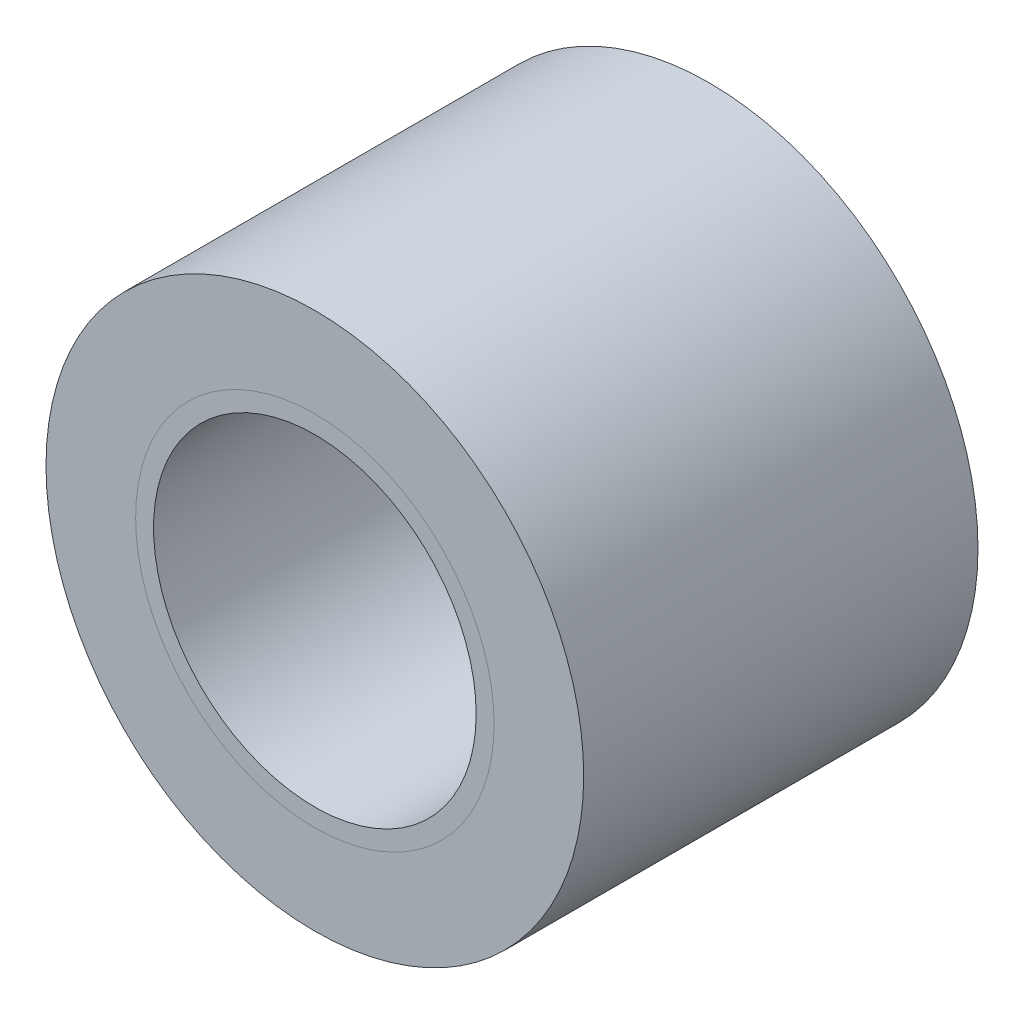
SolidWorks part; units mm, degrees
ref_plane "Plan de face" through (0, 0, 0) normal (0, 0, 1) x (1, 0, 0)
ref_plane "Plan de dessus" through (0, 0, 0) normal (0, 1, 0) x (1, 0, 0)
ref_plane "Plan de droite" through (0, 0, 0) normal (1, 0, 0) x (0, 0, -1)
sketch "Esquisse1" plane through (0, 0, 0) normal (0, 0, 1) x (1, 0, 0)
  circle A0 centre (0, 0) radius 15
  circle A1 centre (0, 0) radius 10
  circle A2 centre (0, 0) radius 9
  dimension "D1" = 18
  dimension "D2" = 30
  dimension "D3" = 20
extrude "Boss.-Extru.1" add sketch "Esquisse1" along normal blind 22 contours A0 A1 region at (-14.5757, 0, 0)
extrude "Boss.-Extru.2" add sketch "Esquisse1<3>" along normal blind 22 separate body contours A2 | A1
sketch "Esquisse1<3>" plane through (0, 0, 0) normal (0, 0, 1) x (1, 0, 0) same geometry as "Esquisse1"
extrude "Boss.-Extru.3" add sketch "Esquisse1<4>" along normal blind 7.5 separate body contours A2 region at (0, 0, 0)
sketch "Esquisse1<4>" plane through (0, 0, 0) normal (0, 0, 1) x (1, 0, 0) same geometry as "Esquisse1"
sketch "Esquisse2" plane through (0, 0, 0) normal (0, 0, -1) x (-1, 0, 0)
  circle A0 centre (0, 0) radius 1.5
  dimension "D1" = 3
extrude "Enlèv. mat.-Extru.1" cut sketch "Esquisse2" against normal through all
